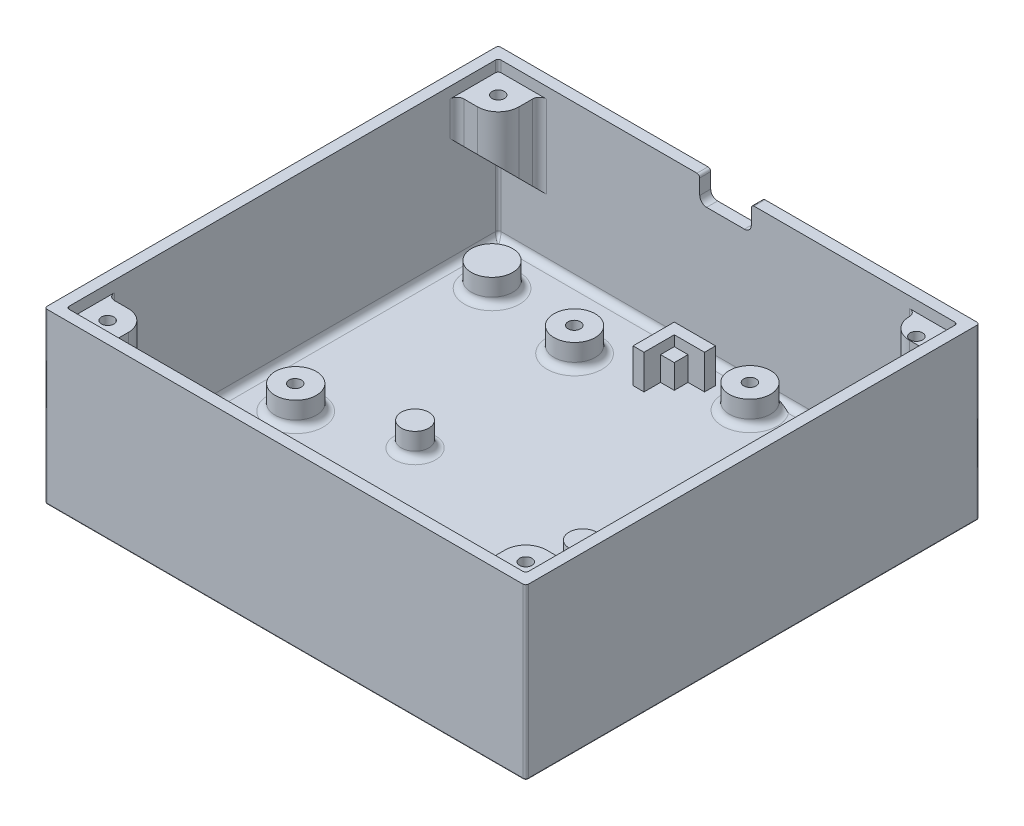
SolidWorks part; units mm, degrees
ref_plane "前视基准面" through (0, 0, 0) normal (0, 0, 1) x (1, 0, 0)
ref_plane "上视基准面" through (0, 0, 0) normal (0, 1, 0) x (1, 0, 0)
ref_plane "右视基准面" through (0, 0, 0) normal (1, 0, 0) x (0, 0, -1)
other "Configuration Table"
sketch "草图1" plane through (0, 0, 0) normal (0, 1, 0) x (1, 0, 0)
  line L1 (0, 0) -> (70, 0)
  line L2 (0, 0) -> (0, 66)
  line L3 (0, 66) -> (70, 66)
  line L4 (70, 0) -> (70, 66)
  dimension "D1" = 70
  dimension "D2" = 66
extrude "凸台-拉伸1" add sketch "草图1" along normal blind 2
sketch "草图2" plane through (0, 2, 0) normal (0, 1, 0) x (1, 0, 0)
  line L0 (70, 0) -> (70, 66) construction
  line L1 (66.8, 60) -> (31.6, 60)
  line L2 (66.8, 60) -> (66.8, 6)
  line L3 (66.8, 6) -> (31.6, 6)
  line L4 (31.6, 60) -> (31.6, 6)
  line L5 (70, 66) -> (0, 66) construction
  line L11 (68.4, 61.6) -> (30, 61.6)
  line L12 (30, 61.6) -> (30, 4.4)
  line L13 (68.4, 4.4) -> (30, 4.4)
  line L14 (68.4, 61.6) -> (68.4, 4.4)
  dimension "D1" = 35.2
  dimension "D2" = 54
  dimension "D3" = 3.2
  dimension "D4" = 6
  dimension "D5" = 1.6
extrude "凸台-拉伸2" add sketch "草图2" along normal blind 5
sketch "草图3" plane through (0, 2, 0) normal (0, 1, 0) x (1, 0, 0)
  line L0 (31.6, 6) -> (66.8, 6) construction
  line L1 (31.6, 60) -> (33.6, 60)
  line L2 (31.6, 60) -> (31.6, 58)
  line L3 (31.6, 58) -> (33.6, 58)
  line L4 (33.6, 60) -> (33.6, 58)
  line L5 (66.8, 60) -> (64.8, 60)
  line L6 (66.8, 60) -> (66.8, 58)
  line L7 (66.8, 58) -> (64.8, 58)
  line L8 (64.8, 60) -> (64.8, 58)
  line L9 (31.6, 6) -> (33.6, 6)
  line L10 (31.6, 6) -> (31.6, 8)
  line L11 (31.6, 8) -> (33.6, 8)
  line L12 (33.6, 6) -> (33.6, 8)
  line L13 (66.8, 6) -> (64.8, 6)
  line L14 (66.8, 6) -> (66.8, 8)
  line L15 (66.8, 8) -> (64.8, 8)
  line L16 (64.8, 6) -> (64.8, 8)
  line L17 (66.8, 6) -> (66.8, 60) construction
  circle A0 centre (49.3, 29) radius 2
  dimension "D9" = 4
  dimension "D11" = 17.5
  dimension "D1" = 2
  dimension "D2" = 2
  dimension "D3" = 2
  dimension "D4" = 2
  dimension "D5" = 2
  dimension "D6" = 2
  dimension "D7" = 2
  dimension "D8" = 2
  dimension "D10" = 23
extrude "凸台-拉伸3" add sketch "草图3" along normal blind 3.5
sketch "草图4" plane through (0, 7, 0) normal (0, 1, 0) x (1, 0, 0)
  line L0 (68.4, 61.6) -> (30, 61.6) construction
  line L1 (36, 61.6) -> (62.4, 61.6)
  line L2 (36, 61.6) -> (36, 60)
  line L3 (36, 60) -> (62.4, 60)
  line L4 (62.4, 61.6) -> (62.4, 60)
  line L5 (64.8, 60) -> (33.6, 60) construction
  line L6 (30, 61.6) -> (30, 4.4) construction
  line L7 (30, 55.6) -> (31.6, 55.6)
  line L8 (30, 55.6) -> (30, 10.4)
  line L9 (30, 10.4) -> (31.6, 10.4)
  line L10 (31.6, 55.6) -> (31.6, 10.4)
  line L11 (31.6, 58) -> (31.6, 8) construction
  line L12 (31.6, 6) -> (66.8, 6) construction
  line L13 (36, 6) -> (62.4, 6)
  line L14 (36, 6) -> (36, 4.4)
  line L15 (36, 4.4) -> (62.4, 4.4)
  line L16 (62.4, 6) -> (62.4, 4.4)
  line L17 (30, 4.4) -> (68.4, 4.4) construction
  line L18 (30, 61.6) -> (30, 4.4) construction
  line L19 (68.4, 4.4) -> (68.4, 61.6) construction
  line L20 (66.8, 6) -> (66.8, 60) construction
  line L21 (66.8, 55.6) -> (68.4, 55.6)
  line L22 (66.8, 55.6) -> (66.8, 10.4)
  line L23 (66.8, 10.4) -> (68.4, 10.4)
  line L24 (68.4, 55.6) -> (68.4, 10.4)
  line L25 (68.4, 61.6) -> (30, 61.6) construction
  dimension "D1" = 6
  dimension "D2" = 6
  dimension "D3" = 6
  dimension "D4" = 6
  dimension "D5" = 6
  dimension "D6" = 6
  dimension "D7" = 6
  dimension "D8" = 6
extrude "切除-拉伸1" cut sketch "草图4" against normal up to surface (5 mm away) up to face at (35, 2, -33)
sketch "草图7" plane through (0, 2, 0) normal (0, 1, 0) x (1, 0, 0)
  line L0 (30, 4.4) -> (36, 4.4) construction
  line L2 (30, 10.4) -> (30, 4.4) construction
  circle A3 centre (22, 31.9) radius 2
  dimension "D1" = 27.5
  dimension "D7" = 4
  dimension "D9" = 8
extrude "凸台-拉伸5" add sketch "草图7" along normal blind 3.5
sketch "草图8" plane through (0, 2, 0) normal (0, 1, 0) x (1, 0, 0)
  line L0 (70, 66) -> (0, 66) construction
  line L1 (30, 10.4) -> (30, 4.4) construction
  line L2 (30, 61.6) -> (30, 55.6) construction
  line L3 (30, 4.4) -> (36, 4.4) construction
  line L4 (36, 61.6) -> (30, 61.6) construction
  line L5 (68.4, 4.4) -> (68.4, 10.4) construction
  line L6 (62.4, 6) -> (66.8, 6) construction
  line L8 (31.6, 60) -> (31.6, 55.6) construction
  line L9 (36, 60) -> (31.6, 60) construction
  circle A1 centre (7.5, 57.6) radius 3
  circle A3 centre (24, 14.4) radius 2
  circle A5 centre (6.3, 11.4) radius 3
  circle A6 centre (8.7, 27.85) radius 3
  circle A7 centre (21.7, 55.4) radius 3
  circle A8 centre (49.4, 5) radius 3
  circle A9 centre (41.6, 61) radius 3
  dimension "D3" = 21.3
  dimension "D4" = 6
  dimension "D7" = 4
  dimension "D8" = 6
  dimension "D9" = 10
  dimension "D10" = 6
  dimension "D11" = 23.7
  dimension "D12" = 7
  dimension "D13" = 6
  dimension "D14" = 6
  dimension "D16" = 10.6
  dimension "D5" = 22.5
  dimension "D6" = 4
  dimension "D17" = 6
  dimension "D18" = 19
  dimension "D19" = 1
  dimension "D20" = 6
  dimension "D21" = 10
  dimension "D22" = 1
  dimension "D23" = 8.3
  dimension "0" = 38.15
extrude "凸台-拉伸9" add sketch "草图8" along normal blind 3.5
sketch "草图9" plane through (0, 2, 0) normal (0, 1, 0) x (1, 0, 0)
  line L0 (1.6, 64.4) -> (1.6, 1.6)
  line L1 (0, 66) -> (70, 66)
  line L2 (0, 66) -> (0, 0)
  line L3 (0, 0) -> (70, 0)
  line L4 (70, 66) -> (70, 0)
  line L5 (1.6, 1.6) -> (68.4, 1.6)
  line L6 (68.4, 64.4) -> (68.4, 1.6)
  line L7 (1.6, 64.4) -> (68.4, 64.4)
  line L8 (70, 0) -> (70, 66) construction
  line L9 (0, 0) -> (70, 0) construction
  dimension "D2" = 0
  dimension "D3" = 0
  dimension "D1" = 1.6
extrude "凸台-拉伸13" add sketch "草图9" along normal blind 21
sketch "草图11" plane through (0, 23, 0) normal (0, 1, 0) x (1, 0, 0)
  line L0 (68.4, 64.4) -> (1.6, 64.4) construction
  line L1 (68.4, 64.4) -> (62.4, 64.4)
  line L2 (68.4, 64.4) -> (68.4, 60.4)
  line L3 (68.4, 60.4) -> (62.4, 60.4)
  line L4 (62.4, 64.4) -> (62.4, 60.4)
  line L5 (68.4, 61.6) -> (68.4, 64.4) construction
  line L7 (68.4, 1.6) -> (62.4, 1.6)
  line L8 (68.4, 1.6) -> (68.4, 7.6)
  line L9 (68.4, 7.6) -> (62.4, 7.6)
  line L10 (62.4, 1.6) -> (62.4, 7.6)
  line L11 (1.6, 1.6) -> (7.6, 1.6)
  line L12 (1.6, 1.6) -> (1.6, 7.6)
  line L13 (1.6, 7.6) -> (7.6, 7.6)
  line L14 (7.6, 1.6) -> (7.6, 7.6)
  line L15 (1.6, 64.4) -> (7.6, 64.4)
  line L16 (1.6, 64.4) -> (1.6, 58.4)
  line L17 (1.6, 58.4) -> (7.6, 58.4)
  line L18 (7.6, 64.4) -> (7.6, 58.4)
  dimension "D1" = 4
  dimension "D2" = 6
  dimension "D3" = 6
  dimension "D4" = 6
  dimension "D5" = 6
  dimension "D6" = 6
  dimension "D7" = 6
  dimension "D8" = 6
extrude "凸台-拉伸14" add sketch "草图11" against normal blind 6
chamfer "倒角1" distance 6 angle 45 4 edges at (65.4, 17, -64.4) (4.6, 17, -64.4) (65.4, 17, -1.6) (4.6, 17, -1.6)
sketch "草图12" plane through (0, 23, 0) normal (0, 1, 0) x (1, 0, 0)
  line L0 (1.6, 64.4) -> (1.6, 1.6)
  line L1 (0, 66) -> (70, 66)
  line L2 (0, 66) -> (0, 0)
  line L3 (0, 0) -> (70, 0)
  line L4 (70, 66) -> (70, 0)
  line L5 (1.6, 1.6) -> (68.4, 1.6)
  line L6 (68.4, 64.4) -> (68.4, 1.6)
  line L7 (1.6, 64.4) -> (68.4, 64.4)
  dimension "D1" = 1.6
extrude "凸台-拉伸15" add sketch "草图12" along normal blind 1.6
sketch "草图13" plane through (0, 23, 0) normal (0, 1, 0) x (1, 0, 0)
  line L0 (1.6, 58.4) -> (7.6, 58.4) construction
  line L1 (7.6, 58.4) -> (7.6, 64.4) construction
  circle A0 centre (4.6, 61.4) radius 0.9
  circle A1 centre (65.4, 61.4) radius 0.9
  circle A2 centre (65.4, 4.6) radius 0.9
  circle A3 centre (4.6, 4.6) radius 0.9
  dimension "D1" = 1.8
  dimension "D2" = 3
  dimension "D3" = 3
  dimension "D4" = 2
  dimension "D5" = 2
extrude "切除-拉伸3" cut sketch "草图13" against normal blind 6
sketch "草图14" plane through (0, 0, -64.4) normal (0, 0, 1) x (1, 0, 0)
  line L1 (30.9, 24.6) -> (38.4, 24.6)
  line L2 (30.9, 24.6) -> (30.9, 21)
  line L3 (30.9, 21) -> (38.4, 21)
  line L4 (38.4, 24.6) -> (38.4, 21)
  line L5 (68.4, 24.6) -> (1.6, 24.6) construction
  dimension "D1" = 3.6
  dimension "D2" = 7.5
  dimension "D3" = 0
  dimension "D4" = 30
extrude "切除-拉伸4" cut sketch "草图14" against normal blind 6
fillet "圆角1" radius 1 37 edges at (33.6, 2, -7) (32.6, 2, -8) (31.6, 2, -9.2) (30.8, 2, -10.4) (30, 2, -7.4) (33, 2, -4.4) (36, 2, -5.2) (34.8, 2, -6) (22, 2, -33.9) (7.5, 2, -60.6) (24, 2, -16.4) (6.3, 2, -14.4) (49.4, 2, -8) (41.6, 2, -64) (49.3, 2, -31) (21.7, 2, -58.4) (8.7, 2, -30.85) (65.4, 2, -4.4) (62.4, 2, -5.2) (63.6, 2, -6) (64.8, 2, -7) (65.8, 2, -8) (66.8, 2, -9.2) (67.6, 2, -10.4) (65.4, 2, -61.6) (67.6, 2, -55.6) (66.8, 2, -56.8) (65.8, 2, -58) (64.8, 2, -59) (63.6, 2, -60) (62.4, 2, -60.8) (35, 2, -64.4) (68.4, 2, -63) (68.4, 2, -33) (68.4, 2, -3) (35, 2, -1.6) (1.6, 2, -33)
sketch "草图16" plane through (0, 5.5, 0) normal (0, 1, 0) x (1, 0, 0)
  circle A0 centre (8.6825, 27.7876) radius 0.9
  dimension "D1" = 1.8
extrude "切除-拉伸5" cut sketch "草图16" against normal blind 6
fillet "圆角2" radius 1 2 edges at (38.4, 21, -65.2) (30.9, 21, -65.2)
fillet "圆角3" radius 3 4 edges at (7.6, 20, -7.6) (62.4, 20, -7.6) (62.4, 19, -60.4) (7.6, 20, -58.4)
fillet "圆角4" radius 1 8 edges at (1.6, 20, -7.6) (7.6, 17, -1.6) (62.4, 17, -1.6) (68.4, 20, -7.6) (68.4, 19, -60.4) (62.4, 17, -64.4) (1.6, 20, -58.4) (7.6, 17, -64.4)
fillet "圆角5" radius 0.4 18 edges at (68.1071, 2.2929, -64.1071) (1.8929, 2.2929, -64.1071) (1.8929, 2.2929, -1.8929) (68.1071, 2.2929, -1.8929) (68.4, 23.8, -1.6) (68.4, 7, -64.4) (68.4, 23.8, -64.4) (1.6, 23.8, -64.4) (1.6, 7, -64.4) (1.6, 23.8, -1.6) (1.6, 7, -1.6) (68.4, 7, -1.6) (0, 12.3, 0) (70, 12.3, 0) (70, 12.3, -66) (0, 12.3, -66) (30.9, 24.6, -65.2) (38.4, 24.6, -65.2)
fillet "圆角6" radius 0.2 9 edges at (69.8828, 0, -0.1172) (70, 0, -33) (69.8828, 0, -65.8828) (35, 0, -66) (0.1172, 0, -65.8828) (0, 0, -33) (0.1172, 0, -0.1172) (35, 0, 0) (8.6825, 0, -28.6876)
sketch "草图17" plane through (0, 5.5, 0) normal (0, 1, 0) x (1, 0, 0)
  circle A0 centre (21.6329, 55.4189) radius 0.9
  dimension "D1" = 1.8
extrude "切除-拉伸6" cut sketch "草图17" against normal blind 6
sketch "草图18" plane through (0, 5.5, 0) normal (0, 1, 0) x (1, 0, 0)
  circle A0 centre (41.6, 61) radius 0.9
  circle A1 centre (49.4, 5) radius 0.9
  dimension "D1" = 1.8
  dimension "D2" = 1.8
extrude "切除-拉伸7" cut sketch "草图18" against normal blind 6
